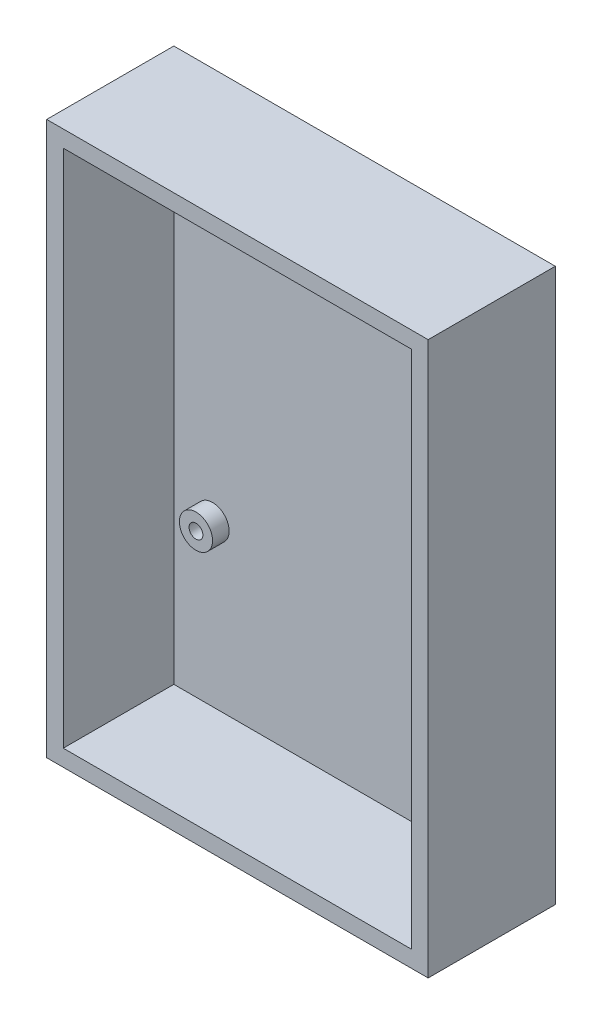
SolidWorks part; units mm, degrees
ref_plane "Ön Düzlem" through (0, 0, 0) normal (0, 0, 1) x (1, 0, 0)
ref_plane "Üst Düzlem" through (0, 0, 0) normal (0, 1, 0) x (1, 0, 0)
ref_plane "Sağ Düzlem" through (0, 0, 0) normal (1, 0, 0) x (0, 0, -1)
sketch "Çizim1" plane through (0, 0, 0) normal (0, 0, 1) x (1, 0, 0)
  line L0 (-34.5, 50) -> (34.5, -50) construction
  line L1 (-34.5, 50) -> (34.5, 50)
  line L2 (-34.5, 50) -> (-34.5, -50)
  line L3 (-34.5, -50) -> (34.5, -50)
  line L4 (34.5, 50) -> (34.5, -50)
  dimension "D1" = 100
  dimension "D2" = 69
extrude "Yükseklik-Ekstrüzyon1" add sketch "Çizim1" along normal blind 3
sketch "Çizim2" plane through (0, 0, 3) normal (0, 0, 1) x (1, 0, 0)
  line L0 (34.5, 50) -> (-34.5, 50) construction
  line L1 (-34.5, 50) -> (-34.5, -50) construction
  circle A0 centre (-24.5, 40) radius 1.25
  circle A1 centre (-24.5, 40) radius 3
  circle A2 centre (24.5, 40) radius 3
  circle A3 centre (24.5, 40) radius 1.25
  circle A4 centre (24.5, -18) radius 3
  circle A5 centre (24.5, -18) radius 1.25
  circle A6 centre (-24.5, -18) radius 3
  circle A7 centre (-24.5, -18) radius 1.25
  dimension "D1" = 2
  dimension "D3" = 10
  dimension "D4" = 10
  dimension "D2" = 2
extrude "Yükseklik-Ekstrüzyon2" add sketch "Çizim2" along normal blind 3
sketch "Çizim3" plane through (0, 0, 3) normal (0, 0, 1) x (1, 0, 0)
  line L1 (-31.5, 47) -> (-31.5, -47)
  line L2 (-34.5, 50) -> (34.5, 50)
  line L3 (-34.5, 50) -> (-34.5, -50)
  line L4 (-34.5, -50) -> (34.5, -50)
  line L5 (34.5, 50) -> (34.5, -50)
  line L6 (-31.5, -47) -> (31.5, -47)
  line L7 (31.5, 47) -> (31.5, -47)
  line L8 (-31.5, 47) -> (31.5, 47)
  dimension "D1" = 3
extrude "Yükseklik-Ekstrüzyon3" add sketch "Çizim3" along normal blind 20
